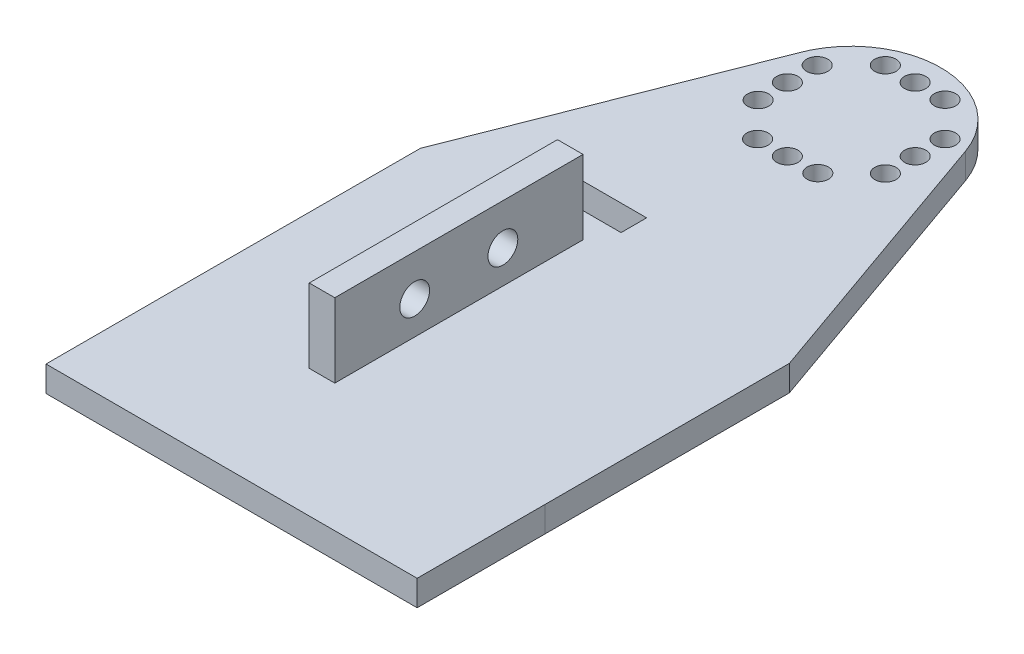
SolidWorks part; units mm, degrees
ref_plane "Front Plane" through (0, 0, 0) normal (0, 0, 1) x (1, 0, 0)
ref_plane "Top Plane" through (0, 0, 0) normal (0, 1, 0) x (1, 0, 0)
ref_plane "Right Plane" through (0, 0, 0) normal (1, 0, 0) x (0, 0, -1)
sketch "Sketch2" plane through (0, 0, 0) normal (0, 1, 0) x (1, 0, 0)
  line L0 (-0.0001, 7.5128) -> (3.4999, 7.5129) construction
  line L1 (0, 0) -> (0, -57.0944) construction
  line L3 (0, 0) -> (7.5, 0.013) construction
  line L5 (0, 0) -> (0.0001, -7.4872) construction
  line L6 (21.1625, -28.4147) -> (9.9242, 3.5128)
  line L7 (-22.3399, -28.2122) -> (-9.9242, 3.5128)
  line L9 (0, 0) -> (0.0001, -7.4872) construction
  line L11 (7.5001, -3.487) -> (7.5001, 3.513) construction
  line L13 (-7.5, 3.5127) -> (-7.5, 0.0127) construction
  line L22 (-22.3884, -57.0944) -> (21.1625, -57.0944)
  line L23 (-22.3884, -57.0944) -> (21.1625, -57.0944) construction
  line L25 (-22.3884, -57.0944) -> (-22.3399, -28.2122)
  line L26 (21.1625, -28.4147) -> (21.1625, -57.0944)
  line L27 (21.1625, -28.4147) -> (-22.3399, -28.2122)
  circle A0 centre (0, 0) radius 10.5276
  circle A1 centre (0.0001, -7.4872) radius 1.25
  circle A2 centre (-7.5, 0.0127) radius 1.25
  circle A3 centre (-0.0001, 7.5128) radius 1.25
  circle A4 centre (7.5, 0.013) radius 1.25
  circle A5 centre (-7.4282, -3.4865) radius 1.25
  circle A6 centre (-7.5, 3.5127) radius 1.25
  circle A7 centre (-3.5001, 7.5128) radius 1.25
  circle A8 centre (3.4999, 7.5129) radius 1.25
  circle A9 centre (7.5001, 3.513) radius 1.25
  circle A10 centre (7.5001, -3.487) radius 1.25
  circle A11 centre (-3.4999, -7.4872) radius 1.25
  circle A12 centre (3.4994, -7.4154) radius 1.25
extrude "Boss-Extrude1" add sketch "Sketch2" against normal blind 3 contours L26 L27 L25 L22 | A0 L27 | A0 A12 A11 A10 A9 A8 A7 A6 A5 A4 A3 A1 region at (-0.0012, 0, 0.0038) region at (-0.4242, 0, 18.1835) region at (-0.6264, 0, 42.7065)
sketch "Sketch6" plane through (0, -3, 0) normal (0, -1, 0) x (1, 0, 0)
  line L0 (-22.3884, 57.0944) -> (-6.5, 57.0944) construction
  line L1 (-22.3884, 57.0944) -> (21.1625, 57.0944) construction
  line L2 (-22.3884, 57.0944) -> (-6.5, 57.0944) construction
  line L3 (-6.5, 57.0944) -> (-3.5, 57.0944) construction
  line L4 (-3.5, 57.0944) -> (-3.5, 27.9644) construction
  line L5 (-3.5, 27.9644) -> (-6.5, 27.9644) construction
  line L6 (-6.5, 27.9644) -> (-6.5, 57.0944) construction
  line L7 (-6.5, 57.0944) -> (-6.5, 27.9644)
  line L8 (-6.5, 27.9644) -> (-3.5, 27.9644)
  line L9 (-3.5, 27.9644) -> (-3.5, 57.0944)
  line L10 (-3.5, 57.0944) -> (-6.5, 57.0944)
  line L17 (-3.5, 27.9644) -> (-6.5, 27.9644) construction
  line L19 (-6.5, 27.9644) -> (-3.5, 27.9644) construction
extrude "Boss-Extrude3" add sketch "Sketch6" against normal blind 11.68
sketch "Sketch9" plane through (-3.5, 0, 0) normal (1, 0, 0) x (0, 0, -1)
  line L0 (-37.3694, 3.88) -> (-37.3694, 0) construction
  line L1 (-57.0944, 0) -> (-27.9644, 0) construction
  line L4 (-37.3694, 3.88) -> (-47.7194, 3.88) construction
  circle A0 centre (-37.3694, 3.88) radius 1.75
  circle A1 centre (-47.7194, 3.88) radius 1.75
extrude "Cut-Extrude2" cut sketch "Sketch9" against normal blind 5
sketch "Sketch10" plane through (0, 0, 57.0944) normal (0, 0, 1) x (1, 0, 0)
  line L0 (-22.3884, 0) -> (-6.5, 0)
  line L1 (-6.5, 0) -> (-3.5, 0)
  line L4 (-3.5, 0) -> (21.1625, 0)
  line L5 (21.1625, 0) -> (21.1625, -3)
  line L6 (21.1625, -3) -> (-22.3884, -3)
  line L7 (-22.3884, -3) -> (-22.3884, 0)
extrude "Boss-Extrude4" add sketch "Sketch10" along normal blind 15
sketch "Sketch11" plane through (0, 0, 0) normal (0, 1, 0) x (1, 0, 0)
  line L0 (0, 0) -> (0, -25) construction
  line L1 (0, -25) -> (-2, -25) construction
  line L2 (-2, -25) -> (-10, -25) construction
  line L3 (-10, -25) -> (-2, -25)
  line L4 (-2, -25) -> (-2, -22)
  line L5 (-2, -22) -> (-10, -22)
  line L6 (-10, -22) -> (-10, -25)
extrude "Cut-Extrude4" cut sketch "Sketch11" against normal blind 10
